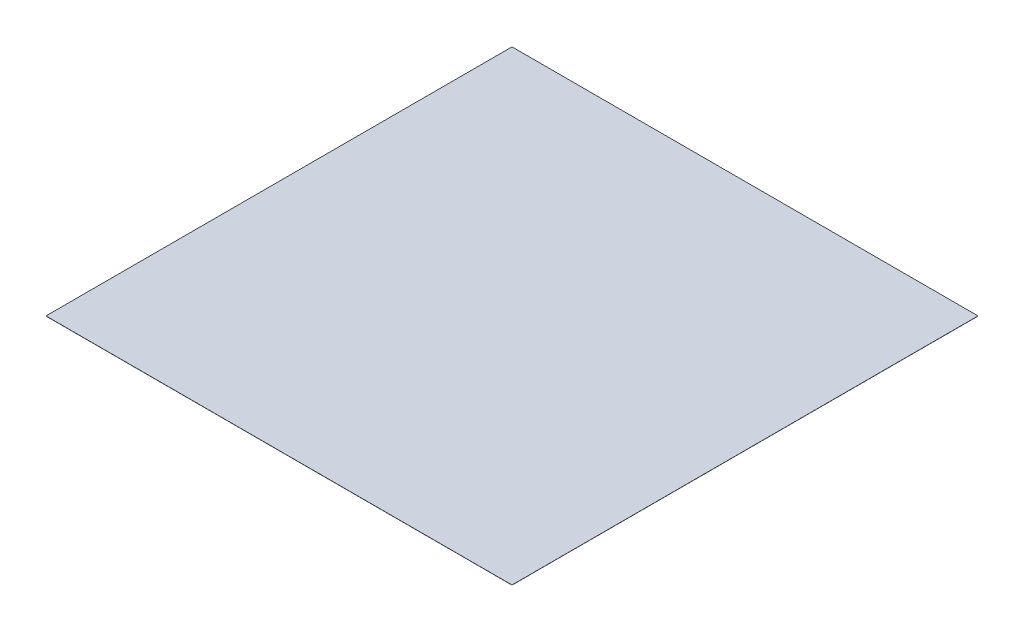
SolidWorks part; units mm, degrees
ref_plane "Front Plane" through (0, 0, 0) normal (0, 0, 1) x (1, 0, 0)
ref_plane "Top Plane" through (0, 0, 0) normal (0, 1, 0) x (1, 0, 0)
ref_plane "Right Plane" through (0, 0, 0) normal (1, 0, 0) x (0, 0, -1)
sketch "Sketch1" plane through (0, 0, 0) normal (0, 1, 0) x (1, 0, 0)
  line L1 (-3810, 3810) -> (3810, 3810)
  line L2 (-3810, 3810) -> (-3810, -3810)
  line L3 (-3810, -3810) -> (3810, -3810)
  line L4 (3810, 3810) -> (3810, -3810)
  line L5 (-3810, 3810) -> (3810, -3810) construction
  line L6 (-3810, -3810) -> (3810, 3810) construction
  point P0 (0, 0)
  dimension "D1" = 7620
  dimension "D2" = 7620
extrude "Boss-Extrude1" add sketch "Sketch1" along normal blind 2.54
